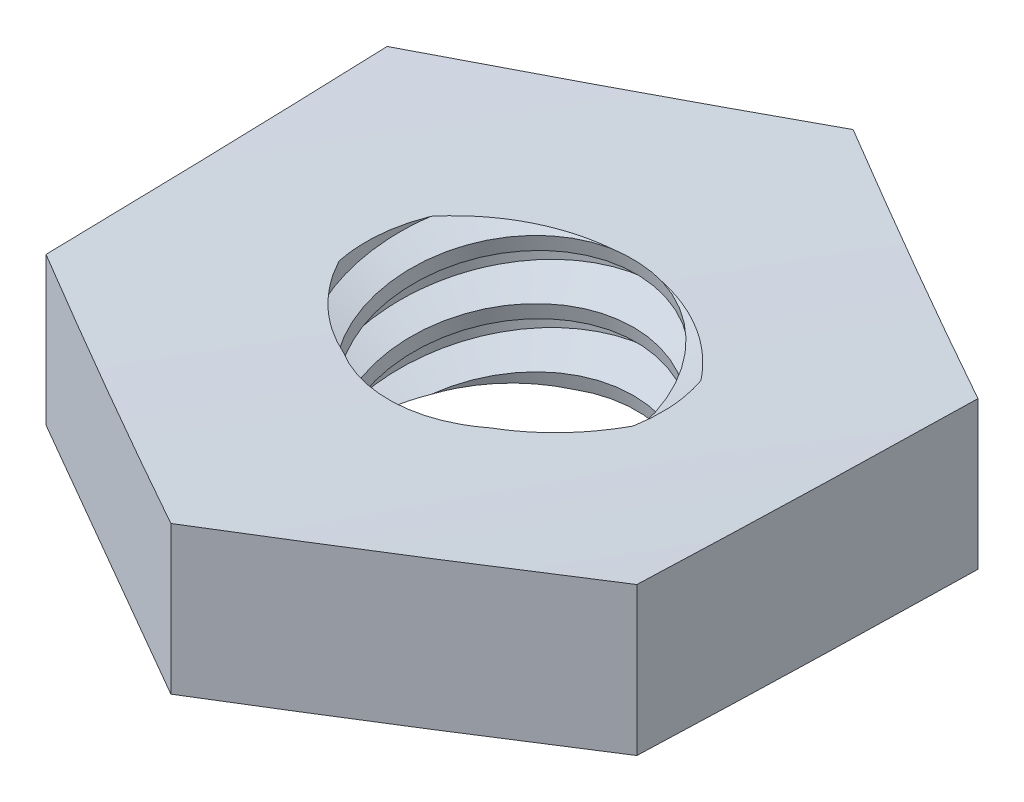
SolidWorks part; units mm, degrees
ref_plane "Front" through (0, 0, 0) normal (0, 0, 1) x (1, 0, 0)
ref_plane "Top" through (0, 0, 0) normal (0, 1, 0) x (1, 0, 0)
ref_plane "Right" through (0, 0, 0) normal (1, 0, 0) x (0, 0, -1)
sketch "Sketch1" plane through (0, 0, 0) normal (0, 1, 0) x (1, 0, 0)
  line L1 (0, 2.3094) -> (-2, 1.1547)
  line L2 (-2, 1.1547) -> (-2, -1.1547)
  line L3 (-2, -1.1547) -> (0, -2.3094)
  line L4 (0, -2.3094) -> (2, -1.1547)
  line L5 (2, -1.1547) -> (2, 1.1547)
  line L6 (2, 1.1547) -> (0, 2.3094)
  circle A0 centre (0, 0) radius 2 construction
  dimension "Hex Flats" = 4
extrude "Extrude1" add sketch "Sketch1" along normal mid plane 1.6
sketch "Sketch2" plane through (0, 0, 0) normal (1, 0, 0) x (0, 0, -1)
  line L0 (-1, -0.8) -> (-1, 0.8) construction
  line L1 (0, -0.8) -> (1, -0.8)
  line L2 (0, -0.8) -> (0, 0.8)
  line L3 (0, 0.8) -> (1, 0.8)
  line L4 (1, -0.8) -> (1, 0.8)
  line L5 (-1.1547, 0.8) -> (1.1547, 0.8) construction
  line L6 (-1.1547, -0.8) -> (1.1547, -0.8) construction
  line L7 (0, -1.8) -> (0, -0.8) construction
  dimension "Thread Dia" = 2
revolve "Revolve1" add sketch "Sketch2" angle 360 about L7
sketch "Sketch3" plane through (0, 0, 0) normal (1, 0, 0) x (0, 0, -1)
  line L0 (1, 0.8) -> (-1, 0.8) construction
  line L1 (-1, 0.8) -> (-1, 0.4) construction
  line L2 (-1, 0.4) -> (1, 0.8) construction
  line L3 (1, 0.8) -> (1.0098, 0.751) construction
  line L4 (1.0098, 0.751) -> (1.0784, 0.4078)
  line L5 (1.0784, 0.4078) -> (0.8416, 0.4879)
  line L6 (0.8416, 0.4879) -> (0.822, 0.5859)
  line L7 (0.822, 0.5859) -> (1.0098, 0.751)
  line L8 (0.8318, 0.5369) -> (1.0441, 0.5794) construction
  line L9 (1, 0.8) -> (1, 0.5705) construction
  line L10 (1, 0.5705) -> (-1, 0.1705) construction
  line L11 (-1, 0.1705) -> (-1, 0.4) construction
  line L12 (-0.0859, 0.8) -> (0.0859, -0.0589) construction
  line L13 (-1, -0.8) -> (-1, 0.8) construction
  line L14 (0, 0.8) -> (1, 0.8) construction
  line L15 (1, -0.8) -> (1, 0.8) construction
  line L16 (0, 0) -> (0, 0.8) construction
  line L17 (-1.0098, 0.751) -> (-1.0784, 0.4078) construction
  line L18 (-0.822, 0.5859) -> (-1.0098, 0.751) construction
  line L19 (-0.8416, 0.4879) -> (-0.822, 0.5859) construction
  line L20 (-1.0784, 0.4078) -> (-0.8416, 0.4879) construction
  line L21 (0.0859, 0.8) -> (-0.0859, -0.0589) construction
  point P13 (0, 0.3705)
  dimension "D1" = 0.05
  dimension "D2" = 0.1
  dimension "Thread Pitch" = 0.4
  dimension "D4" = 60
  dimension "D5" = 0.4
revolve "Cut-Revolve1" cut sketch "Sketch3" angle 360 about L12
pattern_linear "LPattern1" count 4 spacing 0.4 along (0, -1, 0) count 2 spacing 0.4 along (0, 1, 0) of "Cut-Revolve1"
sketch "Sketch4" plane through (0, 0, 0) normal (1, 0, 0) x (0, 0, -1)
  line L0 (0, 0.8) -> (1, 0.8)
  line L1 (1, 0.8) -> (0.822, 0.717)
  line L2 (0.822, 0.717) -> (0.822, -0.717)
  line L3 (0.822, -0.717) -> (1, -0.8)
  line L4 (1, -0.8) -> (0, -0.8)
  line L5 (0, -0.8) -> (0, 0.8)
  line L6 (1, -0.8) -> (1, 0.8) construction
  line L7 (0, 0.8) -> (1, 0.8) construction
  line L8 (0, -0.8) -> (1, -0.8) construction
  line L9 (0, -0.8) -> (0, 0.8) construction
  line L10 (0, 0.8) -> (0, 0.9964) construction
  dimension "D1" = 25
revolve "Cut-Revolve2" cut sketch "Sketch4" angle 360 about L10
combine bodies "Combine1" operation type subtract main body 112 bodies to subtract 111
sketch "Sketch5" plane through (0, 0, 0) normal (1, 0, 0) x (0, 0, -1)
  line L0 (0, -0.8) -> (2, -0.8)
  line L1 (2, -0.8) -> (2.3094, -0.6557)
  line L2 (2.3094, -0.6557) -> (2.3094, 0.6557)
  line L3 (2.3094, 0.6557) -> (2, 0.8)
  line L4 (0, 0.8) -> (0, 2.07)
  line L5 (0, 2.07) -> (3.5794, 2.07)
  line L6 (3.5794, 2.07) -> (3.5794, -2.07)
  line L7 (3.5794, -2.07) -> (0, -2.07)
  line L8 (0, -2.07) -> (0, -0.8)
  line L9 (2, 0.8) -> (2, -0.8) construction
  line L11 (0, -0.8) -> (1, -0.8) construction
  line L12 (2, 0.8) -> (0, 0.8)
  line L13 (2.3094, 0) -> (3.5794, 0) construction
  line L14 (2.3094, 0.8) -> (2.3094, -0.8) construction
  line L15 (0, -0.8) -> (0, 0.8) construction
  line L17 (0, 0) -> (2, 0) construction
  line L22 (0, 0.8) -> (1, 0.8) construction
  dimension "D1" = 25
  dimension "D2" = 1.27
  dimension "D3" = 1.6
sketch "Sketch6" plane through (-1, 0, 1.7321) normal (-0.5, 0, 0.866) x (0.866, 0, 0.5)
  arc A0 (-9.0483, 1.529) -> (9.0483, 1.529) centre (0, 31.1792) ccw construction
  arc A1 (-9.371, 0.582) -> (9.371, 0.582) centre (0, 31.1792) ccw construction
  arc A2 (-9.0483, 1.529) -> (9.0483, 1.529) centre (0, 31.1792) ccw
  arc A3 (-9.371, 0.582) -> (9.371, 0.582) centre (0, 31.1792) ccw
  spline S0 degree 2 poles (9.0483, 1.529) (0.3052, 6.5486) (-9.0483, 1.529) knots 0 0 0 1 1 1
  spline S1 degree 2 poles (-9.371, 0.582) (0.1334, -6.4277) (9.371, 0.582) knots 0 0 0 1 1 1
extrude "Cut-Extrude1" cut sketch "Sketch6" against normal blind 10
sketch "Sketch7" plane through (-1, 0, -1.7321) normal (-0.5, 0, -0.866) x (-0.866, 0, 0.5)
  point P0 (0.032, -0.3466)
equation "\"D1@Sketch3\"=\"Thread Pitch@Sketch3\"/8"
equation "\"D2@Sketch3\"=\"Thread Pitch@Sketch3\"/4"
equation "\"D5@Sketch3\"=\"Thread Pitch@Sketch3\""
equation "\"D4@LPattern1\"=\"Thread Pitch@Sketch3\""
equation "\"D3@LPattern1\"=\"Thread Pitch@Sketch3\""
equation "\"D1@LPattern1\"=\"Height@Extrude1\"/\"Thread Pitch@Sketch3\""
